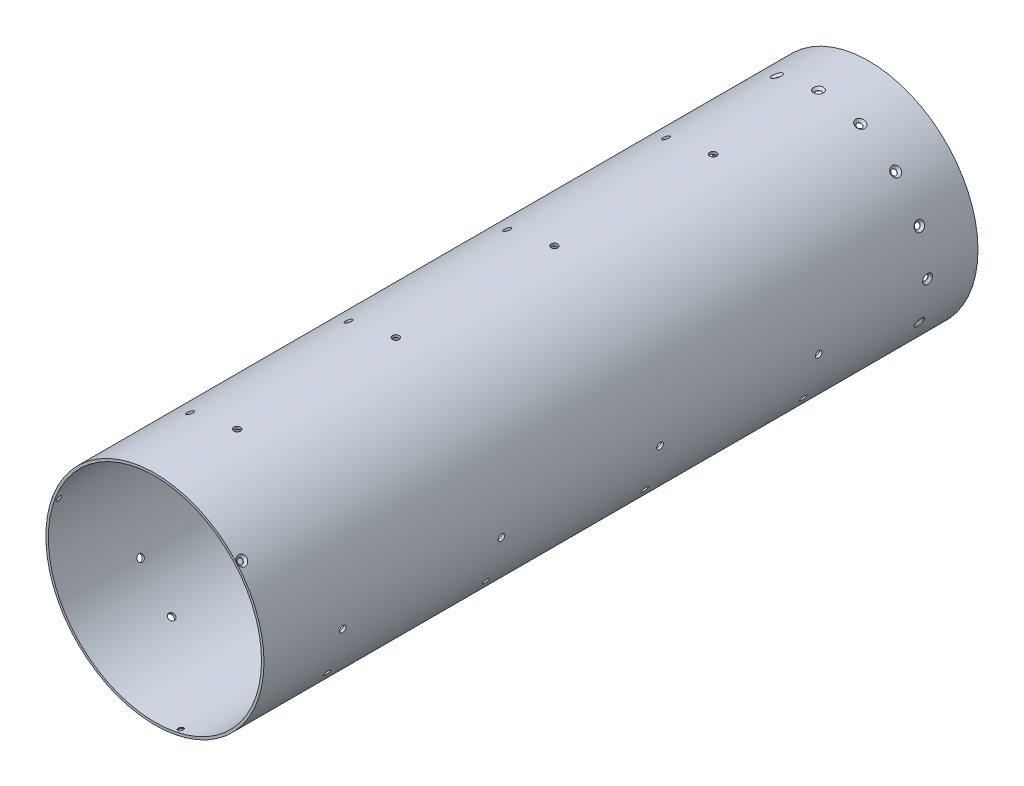
SolidWorks part; units mm, degrees
material "6061-T6 (SS)"
ref_plane "Front Plane" through (0, 0, 0) normal (0, 0, 1) x (1, 0, 0)
ref_plane "Top Plane" through (0, 0, 0) normal (0, 1, 0) x (1, 0, 0)
ref_plane "Right Plane" through (0, 0, 0) normal (1, 0, 0) x (0, 0, -1)
sketch "Sketch1" plane through (0, 0, 0) normal (0, 0, 1) x (1, 0, 0)
  circle A0 centre (0, 0) radius 69.85
  circle A1 centre (0, 0) radius 68.2625
  dimension "D1" = 139.7
  dimension "D2" = 1.5875
extrude "Extrude1" add sketch "Sketch1" along normal blind 457.2
ref_plane "Plane1" through (0, 0, 32.258) normal (0, 0, -1) x (-1, 0, 0)
sketch "Sketch2" plane through (0, 0, 32.258) normal (0, 0, -1) x (-1, 0, 0)
  line L0 (0, 0) -> (0, -69.85) construction
  line L1 (0, 0) -> (-13.6271, -68.5079) construction
  circle A0 centre (0, 0) radius 69.85 construction
  circle A1 centre (0, 0) radius 69.85 construction
  dimension "D1" = 11.25
ref_plane "Plane2" through (0, -69.85, 32.258) normal (0, -1, 0) x (1, 0, 0)
hole_wizard "CSK for M3 Flat Head Machine Screw1" positions "Sketch5" profile "Sketch4" countersink size "M3" standard "Ansi Metric" end condition through all
sketch "Sketch5" plane through (0, -69.85, 32.258) normal (0, -1, 0) x (1, 0, 0)
  point P2 (0, 0)
sketch "Sketch4" plane through (0, -69.85, 32.258) normal (1, 0, 0) x (0, 0, -1)
  line L0 (0, 0) -> (0, 161.1134)
  line L1 (0, 161.1134) -> (1.7, 161.1134)
  line L2 (1.7, 161.1134) -> (1.7, 1.45)
  line L3 (1.7, 1.45) -> (3.15, 0)
  line L5 (3.15, 0) -> (0, 0)
  line L6 (-1.7, 1.45) -> (-3.15, 0) construction
  line L11 (0, -6.35) -> (0, 107.95) construction
  dimension "Thru Hole Dia." = 3.4
  dimension "Thru Hole Depth" = 161.1134
  dimension "Near C'Sink Dia." = 6.3
  dimension "Near C'Sink Angle" = 90
pattern_circular "CirPattern1" count 16 over 360 about axis through (0, 0, 457.2) along (0, 0, -1) of "CSK for M3 Flat Head Machine Screw1"
ref_plane "Plane3" through (0, 0, 446.0875) normal (0, 0, 1) x (1, 0, 0)
ref_plane "Plane5" through (0, 0, 0) normal (0.8315, 0.5556, 0) x (-0.5556, 0.8315, 0)
ref_plane "Plane7" through (0, 0, 0) normal (0.5556, -0.8315, 0) x (0.8315, 0.5556, 0)
ref_plane "Plane9" through (0, 0, 0) normal (-0.1951, -0.9808, 0) x (0.9808, -0.1951, 0)
sketch "Sketch7" plane through (0, 0, 457.2) normal (0, 0, 1) x (1, 0, 0)
  circle A0 centre (0, 0) radius 69.85 construction
  point P0 (69.85, 0)
ref_plane "Plane10" through (13.6271, -68.5079, 32.258) normal (0.1951, -0.9808, 0) x (0.9808, 0.1951, 0)
hole_wizard "#10 Clearance Hole1" positions "Sketch12" profile "Sketch11" hole size "#10" standard "Ansi Inch"
sketch "Sketch12" plane through (13.6271, -68.5079, 32.258) normal (0.1951, -0.9808, 0) x (0.9808, 0.1951, 0)
  point P1 (0, 0)
sketch "Sketch11" plane through (13.6271, -68.5079, 32.258) normal (0, 0, 1) x (0.9808, 0.1951, 0)
  line L0 (0, 0) -> (0, 14.2338)
  line L1 (0, 14.2338) -> (2.5527, 12.7)
  line L2 (2.5527, 12.7) -> (2.5527, 0)
  line L5 (2.5527, 0) -> (0, 0)
  line L10 (0, 14.2338) -> (-2.5527, 12.7) construction
  line L11 (0, -6.35) -> (0, 107.95) construction
  dimension "Hole Dia." = 5.1054
  dimension "Hole Depth" = 12.7
  dimension "Drill Angle" = 118
sketch "Sketch13" plane through (13.6271, -68.5079, 32.258) normal (0.1951, -0.9808, 0) x (0.9808, 0.1951, 0)
  line L0 (0, 0) -> (0, 20.3882) construction
ref_plane "Plane11" through (0, 0, 0) normal (0.9808, 0.1951, 0) x (0, 0, -1)
ref_plane "Plane12" through (0, 0, 454.025) normal (0, 0, 1) x (1, 0, 0)
sketch "Sketch15" plane through (0, 0, 454.025) normal (0, 0, 1) x (1, 0, 0)
  line L0 (0, 0) -> (13.6271, -68.5079) construction
  line L1 (0, 0) -> (0, -69.85) construction
  line L4 (0, -69.8153) -> (0, -68.4) construction
  circle A1 centre (0, 0) radius 69.85 construction
  dimension "D1" = 11.25
ref_plane "Plane13" through (13.6271, -68.5079, 454.025) normal (0.1951, -0.9808, 0) x (0.9808, 0.1951, 0)
hole_wizard "CSK for M3 Flat Head Machine Screw2" positions "Sketch17" profile "Sketch16" countersink size "M3" standard "Ansi Metric"
sketch "Sketch17" plane through (13.6271, -68.5079, 454.025) normal (0.1951, -0.9808, 0) x (0.9808, 0.1951, 0)
  point P7 (0, 0)
sketch "Sketch16" plane through (13.6271, -68.5079, 454.025) normal (0, 0, 1) x (0.9808, 0.1951, 0)
  line L0 (0, 0) -> (0, 8.6415)
  line L1 (0, 8.6415) -> (1.7, 7.62)
  line L2 (1.7, 7.62) -> (1.7, 1.45)
  line L3 (1.7, 1.45) -> (3.15, 0)
  line L5 (3.15, 0) -> (0, 0)
  line L6 (-1.7, 1.45) -> (-3.15, 0) construction
  line L10 (0, 8.6415) -> (-1.7, 7.62) construction
  line L11 (0, -6.35) -> (0, 107.95) construction
  dimension "Hole Dia." = 3.4
  dimension "Hole Depth" = 7.62
  dimension "Near C'Sink Dia." = 6.3
  dimension "Near C'Sink Angle" = 90
  dimension "Drill Angle" = 118
pattern_circular "CirPattern2" count 3 over 360 about axis through (0, 0, 457.2) along (0, 0, -1) of "CSK for M3 Flat Head Machine Screw2"
ref_plane "Plane14" through (0, 0, 406.4) normal (0, 0, 1) x (1, 0, 0)
sketch "Sketch19" plane through (0, 0, 406.4) normal (0, 0, 1) x (1, 0, 0)
  line L0 (0, 0) -> (-13.6271, 68.5079) construction
  line L2 (0, 0) -> (-28.4244, 63.805) construction
  line L3 (0, 0) -> (1.8436, 69.8257) construction
  line L4 (-13.6271, 68.5079) -> (-28.4244, 63.805) construction
  line L5 (-13.6271, 68.5079) -> (1.8436, 69.8257) construction
  line L6 (0, 0) -> (13.6271, -68.5079) construction
  circle A0 centre (0, 0) radius 69.85 construction
  dimension "D1" = 12.762
  dimension "D2" = 30.861
ref_plane "Plane15" through (-28.4244, 63.805, 406.4) normal (-0.4069, 0.9135, 0) x (-0.9135, -0.4069, 0)
ref_plane "Plane16" through (1.8436, 69.8257, 406.4) normal (0.0264, 0.9997, 0) x (-0.9997, 0.0264, 0)
hole_wizard "#6 Clearance Hole1" positions "Sketch21" profile "Sketch22" hole size "#6" standard "Ansi Inch"
sketch "Sketch21" plane through (1.8436, 69.8257, 406.4) normal (0.0264, 0.9997, 0) x (-0.9997, 0.0264, 0)
  point P3 (0, 0)
sketch "Sketch22" plane through (1.8436, 69.8257, 406.4) normal (0, 0, 1) x (-0.9997, 0.0264, 0)
  line L0 (0, 0) -> (0, 13.9934)
  line L1 (0, 13.9934) -> (2.1526, 12.7)
  line L2 (2.1526, 12.7) -> (2.1526, 0)
  line L5 (2.1526, 0) -> (0, 0)
  line L10 (0, 13.9934) -> (-2.1527, 12.7) construction
  line L11 (0, -6.35) -> (0, 107.95) construction
  dimension "Hole Dia." = 4.3053
  dimension "Hole Depth" = 12.7
  dimension "Drill Angle" = 118
hole_wizard "#6 Clearance Hole2" positions "Sketch25" profile "Sketch24" hole size "#6" standard "Ansi Inch"
sketch "Sketch25" plane through (-28.4244, 63.805, 406.4) normal (-0.4069, 0.9135, 0) x (-0.9135, -0.4069, 0)
  point P1 (0, 0)
sketch "Sketch24" plane through (-28.4244, 63.805, 406.4) normal (0, 0, 1) x (-0.9135, -0.4069, 0)
  line L0 (0, 0) -> (0, 13.9934)
  line L1 (0, 13.9934) -> (2.1526, 12.7)
  line L2 (2.1526, 12.7) -> (2.1526, 0)
  line L5 (2.1526, 0) -> (0, 0)
  line L10 (0, 13.9934) -> (-2.1526, 12.7) construction
  line L11 (0, -6.35) -> (0, 107.95) construction
  dimension "Hole Dia." = 4.3053
  dimension "Hole Depth" = 12.7
  dimension "Drill Angle" = 118
pattern_circular "CirPattern3" count 3 over 360 about axis through (0, 0, 457.2) along (0, 0, -1) of "#6 Clearance Hole2", "#6 Clearance Hole1"
pattern_linear "LPattern1" count 4 spacing 101.6 along (0, 0, -1) of "#6 Clearance Hole1", "#6 Clearance Hole2", "CirPattern3"
sketch3d "ref hole"
  line L0 (-40.0918, -55.2068, 101.6) -> (-41.025, -56.4919, 101.6) construction
  spline S0 degree 3 poles (-60.3367, -35.1924, 101.8844) (-60.3367, -35.1924, 101.4578) (-60.3437, -35.1803, 101.3179) (-60.3713, -35.1331, 101.0428) (-60.3921, -35.0973, 100.9061) (-60.4463, -35.0038, 100.6454) (-60.4795, -34.9465, 100.5218) (-60.5575, -34.8111, 100.2878) (-60.6028, -34.7323, 100.177) (-60.7506, -34.4735, 99.8791) (-60.869, -34.2645, 99.7188) (-61.1214, -33.8121, 99.504) (-61.2581, -33.564, 99.4475) (-61.459, -33.1938, 99.4473) (-61.5267, -33.0683, 99.4612) (-61.6569, -32.8248, 99.5162) (-61.7198, -32.7063, 99.5568) (-61.8414, -32.4758, 99.6645) (-61.8999, -32.3641, 99.7319) (-62.0077, -32.1571, 99.8877) (-62.0577, -32.0605, 99.9767) (-62.1497, -31.8817, 100.1775) (-62.1904, -31.8023, 100.2864) (-62.2613, -31.6633, 100.5195) (-62.2918, -31.6032, 100.6453) (-62.3406, -31.5067, 100.9061) (-62.359, -31.4703, 101.0403) (-62.3838, -31.4211, 101.3161) (-62.3902, -31.4084, 101.4588) (-62.3902, -31.4083, 101.7397) (-62.3841, -31.4205, 101.8793) (-62.3594, -31.4696, 102.1568) (-62.3408, -31.5064, 102.293) (-62.2681, -31.6499, 102.6816) (-62.1955, -31.7928, 102.922) (-62.0593, -32.0573, 103.22) (-62.0085, -32.1556, 103.311) (-61.9004, -32.3632, 103.4675) (-61.8431, -32.4727, 103.5337) (-61.7216, -32.7029, 103.6419) (-61.6574, -32.8238, 103.6835) (-61.5276, -33.0665, 103.7385) (-61.4614, -33.1895, 103.7525) (-61.3259, -33.4391, 103.7528) (-61.2586, -33.5623, 103.7389) (-61.1259, -33.8033, 103.6845) (-61.0597, -33.9227, 103.6433) (-60.9325, -34.1507, 103.5354) (-60.8719, -34.2586, 103.4694) (-60.7568, -34.4623, 103.3135) (-60.7019, -34.5587, 103.2226) (-60.6033, -34.7315, 103.0241) (-60.5589, -34.8088, 102.9158) (-60.4803, -34.9452, 102.681) (-60.4466, -35.0034, 102.5554) (-60.3656, -35.143, 102.167) (-60.3367, -35.1924, 101.8844) (-60.3367, -35.1924, 101.4578) (-60.3437, -35.1803, 101.3179) knots -0.0625 -0.0625 0 0 0.03125 0.03125 0.0625 0.0625 0.09375 0.09375 0.125 0.125 0.1875 0.1875 0.25 0.25 0.28125 0.28125 0.3125 0.3125 0.34375 0.34375 0.375 0.375 0.40625 0.40625 0.4375 0.4375 0.46875 0.46875 0.5 0.5 0.53125 0.53125 0.5625 0.5625 0.625 0.625 0.65625 0.65625 0.6875 0.6875 0.71875 0.71875 0.75 0.75 0.78125 0.78125 0.8125 0.8125 0.84375 0.84375 0.875 0.875 0.90625 0.90625 0.9375 0.9375 1 1 1.03125 1.03125 1.0625 only from (-60.3367, -35.1924, 101.6) to (-60.3367, -35.1924, 101.6) construction
  spline S1 degree 3 poles (-39.2832, -57.7568, 101.8844) (-39.2832, -57.7568, 101.4578) (-39.2948, -57.749, 101.3179) (-39.34, -57.7182, 101.0428) (-39.3742, -57.6949, 100.9061) (-39.4635, -57.6339, 100.6454) (-39.518, -57.5965, 100.5218) (-39.6468, -57.5079, 100.2878) (-39.7216, -57.4563, 100.177) (-39.9665, -57.2865, 99.8791) (-40.1634, -57.1489, 99.7188) (-40.5861, -56.8494, 99.504) (-40.8164, -56.6844, 99.4475) (-41.1572, -56.4369, 99.4473) (-41.2723, -56.3528, 99.4612) (-41.4948, -56.1892, 99.5162) (-41.6026, -56.1094, 99.5568) (-41.8117, -55.9537, 99.6645) (-41.9126, -55.8781, 99.7319) (-42.0991, -55.7378, 99.8877) (-42.1858, -55.6722, 99.9767) (-42.3459, -55.5505, 100.1775) (-42.4168, -55.4963, 100.2864) (-42.5407, -55.4015, 100.5195) (-42.5941, -55.3603, 100.6453) (-42.6798, -55.2943, 100.9061) (-42.712, -55.2694, 101.0403) (-42.7556, -55.2357, 101.3161) (-42.7668, -55.227, 101.4588) (-42.7669, -55.227, 101.7397) (-42.7562, -55.2353, 101.8793) (-42.7127, -55.2689, 102.1568) (-42.68, -55.2942, 102.293) (-42.5526, -55.3923, 102.6816) (-42.4255, -55.49, 102.922) (-42.1887, -55.67, 103.22) (-42.1005, -55.7368, 103.311) (-41.9134, -55.8776, 103.4675) (-41.8145, -55.9517, 103.5337) (-41.6057, -56.1071, 103.6419) (-41.4957, -56.1885, 103.6835) (-41.274, -56.3516, 103.7385) (-41.1612, -56.434, 103.7525) (-40.9314, -56.6009, 103.7528) (-40.8175, -56.6831, 103.7389) (-40.594, -56.8434, 103.6845) (-40.4828, -56.9226, 103.6433) (-40.2697, -57.0735, 103.5354) (-40.1686, -57.1448, 103.4694) (-39.9769, -57.279, 103.3135) (-39.8859, -57.3424, 103.2226) (-39.7224, -57.4557, 103.0241) (-39.649, -57.5064, 102.9158) (-39.5193, -57.5956, 102.681) (-39.4639, -57.6336, 102.5554) (-39.3306, -57.7247, 102.167) (-39.2832, -57.7568, 101.8844) (-39.2832, -57.7568, 101.4578) (-39.2948, -57.749, 101.3179) knots -0.0625 -0.0625 0 0 0.03125 0.03125 0.0625 0.0625 0.09375 0.09375 0.125 0.125 0.1875 0.1875 0.25 0.25 0.28125 0.28125 0.3125 0.3125 0.34375 0.34375 0.375 0.375 0.40625 0.40625 0.4375 0.4375 0.46875 0.46875 0.5 0.5 0.53125 0.53125 0.5625 0.5625 0.625 0.625 0.65625 0.65625 0.6875 0.6875 0.71875 0.71875 0.75 0.75 0.78125 0.78125 0.8125 0.8125 0.84375 0.84375 0.875 0.875 0.90625 0.90625 0.9375 0.9375 1 1 1.03125 1.03125 1.0625 only from (-39.2832, -57.7568, 101.6) to (-39.2832, -57.7568, 101.6) construction
  spline S2 degree 3 poles (-60.3367, -35.1924, 101.8844) (-60.3367, -35.1924, 101.4578) (-60.3437, -35.1803, 101.3179) (-60.3713, -35.1331, 101.0428) (-60.3921, -35.0973, 100.9061) (-60.4463, -35.0038, 100.6454) (-60.4795, -34.9465, 100.5218) (-60.5575, -34.8111, 100.2878) (-60.6028, -34.7323, 100.177) (-60.7506, -34.4735, 99.8791) (-60.869, -34.2645, 99.7188) (-61.1214, -33.8121, 99.504) (-61.2581, -33.564, 99.4475) (-61.459, -33.1938, 99.4473) (-61.5267, -33.0683, 99.4612) (-61.6569, -32.8248, 99.5162) (-61.7198, -32.7063, 99.5568) (-61.8414, -32.4758, 99.6645) (-61.8999, -32.3641, 99.7319) (-62.0077, -32.1571, 99.8877) (-62.0577, -32.0605, 99.9767) (-62.1497, -31.8817, 100.1775) (-62.1904, -31.8023, 100.2864) (-62.2613, -31.6633, 100.5195) (-62.2918, -31.6032, 100.6453) (-62.3406, -31.5067, 100.9061) (-62.359, -31.4703, 101.0403) (-62.3838, -31.4211, 101.3161) (-62.3902, -31.4084, 101.4588) (-62.3902, -31.4083, 101.7397) (-62.3841, -31.4205, 101.8793) (-62.3594, -31.4696, 102.1568) (-62.3408, -31.5064, 102.293) (-62.2681, -31.6499, 102.6816) (-62.1955, -31.7928, 102.922) (-62.0593, -32.0573, 103.22) (-62.0085, -32.1556, 103.311) (-61.9004, -32.3632, 103.4675) (-61.8431, -32.4727, 103.5337) (-61.7216, -32.7029, 103.6419) (-61.6574, -32.8238, 103.6835) (-61.5276, -33.0665, 103.7385) (-61.4614, -33.1895, 103.7525) (-61.3259, -33.4391, 103.7528) (-61.2586, -33.5623, 103.7389) (-61.1259, -33.8033, 103.6845) (-61.0597, -33.9227, 103.6433) (-60.9325, -34.1507, 103.5354) (-60.8719, -34.2586, 103.4694) (-60.7568, -34.4623, 103.3135) (-60.7019, -34.5587, 103.2226) (-60.6033, -34.7315, 103.0241) (-60.5589, -34.8088, 102.9158) (-60.4803, -34.9452, 102.681) (-60.4466, -35.0034, 102.5554) (-60.3656, -35.143, 102.167) (-60.3367, -35.1924, 101.8844) (-60.3367, -35.1924, 101.4578) (-60.3437, -35.1803, 101.3179) knots -0.0625 -0.0625 0 0 0.03125 0.03125 0.0625 0.0625 0.09375 0.09375 0.125 0.125 0.1875 0.1875 0.25 0.25 0.28125 0.28125 0.3125 0.3125 0.34375 0.34375 0.375 0.375 0.40625 0.40625 0.4375 0.4375 0.46875 0.46875 0.5 0.5 0.53125 0.53125 0.5625 0.5625 0.625 0.625 0.65625 0.65625 0.6875 0.6875 0.71875 0.71875 0.75 0.75 0.78125 0.78125 0.8125 0.8125 0.84375 0.84375 0.875 0.875 0.90625 0.90625 0.9375 0.9375 1 1 1.03125 1.03125 1.0625 only from (-60.3367, -35.1924, 101.6) to (-60.3367, -35.1924, 101.6)
  spline S3 degree 3 poles (-39.2832, -57.7568, 101.8844) (-39.2832, -57.7568, 101.4578) (-39.2948, -57.749, 101.3179) (-39.34, -57.7182, 101.0428) (-39.3742, -57.6949, 100.9061) (-39.4635, -57.6339, 100.6454) (-39.518, -57.5965, 100.5218) (-39.6468, -57.5079, 100.2878) (-39.7216, -57.4563, 100.177) (-39.9665, -57.2865, 99.8791) (-40.1634, -57.1489, 99.7188) (-40.5861, -56.8494, 99.504) (-40.8164, -56.6844, 99.4475) (-41.1572, -56.4369, 99.4473) (-41.2723, -56.3528, 99.4612) (-41.4948, -56.1892, 99.5162) (-41.6026, -56.1094, 99.5568) (-41.8117, -55.9537, 99.6645) (-41.9126, -55.8781, 99.7319) (-42.0991, -55.7378, 99.8877) (-42.1858, -55.6722, 99.9767) (-42.3459, -55.5505, 100.1775) (-42.4168, -55.4963, 100.2864) (-42.5407, -55.4015, 100.5195) (-42.5941, -55.3603, 100.6453) (-42.6798, -55.2943, 100.9061) (-42.712, -55.2694, 101.0403) (-42.7556, -55.2357, 101.3161) (-42.7668, -55.227, 101.4588) (-42.7669, -55.227, 101.7397) (-42.7562, -55.2353, 101.8793) (-42.7127, -55.2689, 102.1568) (-42.68, -55.2942, 102.293) (-42.5526, -55.3923, 102.6816) (-42.4255, -55.49, 102.922) (-42.1887, -55.67, 103.22) (-42.1005, -55.7368, 103.311) (-41.9134, -55.8776, 103.4675) (-41.8145, -55.9517, 103.5337) (-41.6057, -56.1071, 103.6419) (-41.4957, -56.1885, 103.6835) (-41.274, -56.3516, 103.7385) (-41.1612, -56.434, 103.7525) (-40.9314, -56.6009, 103.7528) (-40.8175, -56.6831, 103.7389) (-40.594, -56.8434, 103.6845) (-40.4828, -56.9226, 103.6433) (-40.2697, -57.0735, 103.5354) (-40.1686, -57.1448, 103.4694) (-39.9769, -57.279, 103.3135) (-39.8859, -57.3424, 103.2226) (-39.7224, -57.4557, 103.0241) (-39.649, -57.5064, 102.9158) (-39.5193, -57.5956, 102.681) (-39.4639, -57.6336, 102.5554) (-39.3306, -57.7247, 102.167) (-39.2832, -57.7568, 101.8844) (-39.2832, -57.7568, 101.4578) (-39.2948, -57.749, 101.3179) knots -0.0625 -0.0625 0 0 0.03125 0.03125 0.0625 0.0625 0.09375 0.09375 0.125 0.125 0.1875 0.1875 0.25 0.25 0.28125 0.28125 0.3125 0.3125 0.34375 0.34375 0.375 0.375 0.40625 0.40625 0.4375 0.4375 0.46875 0.46875 0.5 0.5 0.53125 0.53125 0.5625 0.5625 0.625 0.625 0.65625 0.65625 0.6875 0.6875 0.71875 0.71875 0.75 0.75 0.78125 0.78125 0.8125 0.8125 0.84375 0.84375 0.875 0.875 0.90625 0.90625 0.9375 0.9375 1 1 1.03125 1.03125 1.0625 only from (-39.2832, -57.7568, 101.6) to (-39.2832, -57.7568, 101.6)
  spline S4 degree 3 poles (60.6459, -34.6569, 305.0844) (60.6459, -34.6569, 304.6578) (60.6389, -34.669, 304.5179) (60.6118, -34.7165, 304.2428) (60.5912, -34.7525, 304.1061) (60.5373, -34.8462, 303.8454) (60.5043, -34.9035, 303.7218) (60.4261, -35.0388, 303.4878) (60.3804, -35.1174, 303.377) (60.2303, -35.3748, 303.0791) (60.1084, -35.5818, 302.9188) (59.8429, -36.0266, 302.704) (59.6964, -36.2691, 302.6475) (59.4762, -36.6282, 302.6473) (59.4013, -36.7495, 302.6612) (59.2556, -36.984, 302.7162) (59.1844, -37.0978, 302.7568) (59.0456, -37.3184, 302.8645) (58.9781, -37.4249, 302.9319) (58.8527, -37.6217, 303.0877) (58.7941, -37.7133, 303.1767) (58.6853, -37.8824, 303.3775) (58.6368, -37.9573, 303.4864) (58.5518, -38.0882, 303.7195) (58.515, -38.1447, 303.8453) (58.4559, -38.2352, 304.1061) (58.4336, -38.2693, 304.2403) (58.4033, -38.3154, 304.5161) (58.3956, -38.3273, 304.6588) (58.3955, -38.3273, 304.9397) (58.403, -38.316, 305.0793) (58.4331, -38.27, 305.3568) (58.4558, -38.2355, 305.493) (58.5437, -38.1008, 305.8816) (58.6311, -37.9665, 306.122) (58.7921, -37.7163, 306.42) (58.8518, -37.6232, 306.511) (58.9776, -37.4257, 306.6675) (59.0437, -37.3213, 306.7337) (59.1824, -37.101, 306.8419) (59.255, -36.985, 306.8835) (59.4002, -36.7512, 306.9385) (59.4736, -36.6323, 306.9525) (59.6221, -36.3903, 306.9528) (59.6951, -36.2703, 306.9389) (59.8375, -36.0349, 306.8845) (59.9078, -35.9179, 306.8433) (60.0416, -35.6937, 306.7354) (60.1048, -35.5873, 306.6694) (60.2236, -35.3858, 306.5135) (60.2797, -35.2901, 306.4226) (60.38, -35.1182, 306.2241) (60.4247, -35.0411, 306.1158) (60.5036, -34.9049, 305.881) (60.5371, -34.8466, 305.7554) (60.6175, -34.7066, 305.367) (60.6459, -34.6569, 305.0844) (60.6459, -34.6569, 304.6578) (60.6389, -34.669, 304.5179) knots -0.0625 -0.0625 0 0 0.03125 0.03125 0.0625 0.0625 0.09375 0.09375 0.125 0.125 0.1875 0.1875 0.25 0.25 0.28125 0.28125 0.3125 0.3125 0.34375 0.34375 0.375 0.375 0.40625 0.40625 0.4375 0.4375 0.46875 0.46875 0.5 0.5 0.53125 0.53125 0.5625 0.5625 0.625 0.625 0.65625 0.65625 0.6875 0.6875 0.71875 0.71875 0.75 0.75 0.78125 0.78125 0.8125 0.8125 0.84375 0.84375 0.875 0.875 0.90625 0.90625 0.9375 0.9375 1 1 1.03125 1.03125 1.0625 only from (60.6459, -34.6569, 304.8) to (60.6459, -34.6569, 304.8) construction
  spline S5 degree 3 poles (-60.3367, -35.1924, 305.0844) (-60.3367, -35.1924, 304.6578) (-60.3437, -35.1803, 304.5179) (-60.3713, -35.1331, 304.2428) (-60.3921, -35.0973, 304.1061) (-60.4463, -35.0038, 303.8454) (-60.4795, -34.9465, 303.7218) (-60.5575, -34.8111, 303.4878) (-60.6028, -34.7323, 303.377) (-60.7506, -34.4735, 303.0791) (-60.869, -34.2645, 302.9188) (-61.1214, -33.8121, 302.704) (-61.2581, -33.564, 302.6475) (-61.459, -33.1938, 302.6473) (-61.5267, -33.0683, 302.6612) (-61.6569, -32.8248, 302.7162) (-61.7198, -32.7063, 302.7568) (-61.8414, -32.4758, 302.8645) (-61.8999, -32.3641, 302.9319) (-62.0077, -32.1571, 303.0877) (-62.0577, -32.0605, 303.1767) (-62.1497, -31.8817, 303.3775) (-62.1904, -31.8023, 303.4864) (-62.2613, -31.6633, 303.7195) (-62.2918, -31.6032, 303.8453) (-62.3406, -31.5067, 304.1061) (-62.359, -31.4703, 304.2403) (-62.3838, -31.4211, 304.5161) (-62.3902, -31.4084, 304.6588) (-62.3902, -31.4083, 304.9397) (-62.3841, -31.4205, 305.0793) (-62.3594, -31.4696, 305.3568) (-62.3408, -31.5064, 305.493) (-62.2681, -31.6499, 305.8816) (-62.1955, -31.7928, 306.122) (-62.0593, -32.0573, 306.42) (-62.0085, -32.1556, 306.511) (-61.9004, -32.3632, 306.6675) (-61.8431, -32.4727, 306.7337) (-61.7216, -32.7029, 306.8419) (-61.6574, -32.8238, 306.8835) (-61.5276, -33.0665, 306.9385) (-61.4614, -33.1895, 306.9525) (-61.3259, -33.4391, 306.9528) (-61.2586, -33.5623, 306.9389) (-61.1259, -33.8033, 306.8845) (-61.0597, -33.9227, 306.8433) (-60.9325, -34.1507, 306.7354) (-60.8719, -34.2586, 306.6694) (-60.7568, -34.4623, 306.5135) (-60.7019, -34.5587, 306.4226) (-60.6033, -34.7315, 306.2241) (-60.5589, -34.8088, 306.1158) (-60.4803, -34.9452, 305.881) (-60.4466, -35.0034, 305.7554) (-60.3656, -35.143, 305.367) (-60.3367, -35.1924, 305.0844) (-60.3367, -35.1924, 304.6578) (-60.3437, -35.1803, 304.5179) knots -0.0625 -0.0625 0 0 0.03125 0.03125 0.0625 0.0625 0.09375 0.09375 0.125 0.125 0.1875 0.1875 0.25 0.25 0.28125 0.28125 0.3125 0.3125 0.34375 0.34375 0.375 0.375 0.40625 0.40625 0.4375 0.4375 0.46875 0.46875 0.5 0.5 0.53125 0.53125 0.5625 0.5625 0.625 0.625 0.65625 0.65625 0.6875 0.6875 0.71875 0.71875 0.75 0.75 0.78125 0.78125 0.8125 0.8125 0.84375 0.84375 0.875 0.875 0.90625 0.90625 0.9375 0.9375 1 1 1.03125 1.03125 1.0625 only from (-60.3367, -35.1924, 304.8) to (-60.3367, -35.1924, 304.8) construction
  spline S6 degree 3 poles (-39.2832, -57.7568, 305.0844) (-39.2832, -57.7568, 304.6578) (-39.2948, -57.749, 304.5179) (-39.34, -57.7182, 304.2428) (-39.3742, -57.6949, 304.1061) (-39.4635, -57.6339, 303.8454) (-39.518, -57.5965, 303.7218) (-39.6468, -57.5079, 303.4878) (-39.7216, -57.4563, 303.377) (-39.9665, -57.2865, 303.0791) (-40.1634, -57.1489, 302.9188) (-40.5861, -56.8494, 302.704) (-40.8164, -56.6844, 302.6475) (-41.1572, -56.4369, 302.6473) (-41.2723, -56.3528, 302.6612) (-41.4948, -56.1892, 302.7162) (-41.6026, -56.1094, 302.7568) (-41.8117, -55.9537, 302.8645) (-41.9126, -55.8781, 302.9319) (-42.0991, -55.7378, 303.0877) (-42.1858, -55.6722, 303.1767) (-42.3459, -55.5505, 303.3775) (-42.4168, -55.4963, 303.4864) (-42.5407, -55.4015, 303.7195) (-42.5941, -55.3603, 303.8453) (-42.6798, -55.2943, 304.1061) (-42.712, -55.2694, 304.2403) (-42.7556, -55.2357, 304.5161) (-42.7668, -55.227, 304.6588) (-42.7669, -55.227, 304.9397) (-42.7562, -55.2353, 305.0793) (-42.7127, -55.2689, 305.3568) (-42.68, -55.2942, 305.493) (-42.5526, -55.3923, 305.8816) (-42.4255, -55.49, 306.122) (-42.1887, -55.67, 306.42) (-42.1005, -55.7368, 306.511) (-41.9134, -55.8776, 306.6675) (-41.8145, -55.9517, 306.7337) (-41.6057, -56.1071, 306.8419) (-41.4957, -56.1885, 306.8835) (-41.274, -56.3516, 306.9385) (-41.1612, -56.434, 306.9525) (-40.9314, -56.6009, 306.9528) (-40.8175, -56.6831, 306.9389) (-40.594, -56.8434, 306.8845) (-40.4828, -56.9226, 306.8433) (-40.2697, -57.0735, 306.7354) (-40.1686, -57.1448, 306.6694) (-39.9769, -57.279, 306.5135) (-39.8859, -57.3424, 306.4226) (-39.7224, -57.4557, 306.2241) (-39.649, -57.5064, 306.1158) (-39.5193, -57.5956, 305.881) (-39.4639, -57.6336, 305.7554) (-39.3306, -57.7247, 305.367) (-39.2832, -57.7568, 305.0844) (-39.2832, -57.7568, 304.6578) (-39.2948, -57.749, 304.5179) knots -0.0625 -0.0625 0 0 0.03125 0.03125 0.0625 0.0625 0.09375 0.09375 0.125 0.125 0.1875 0.1875 0.25 0.25 0.28125 0.28125 0.3125 0.3125 0.34375 0.34375 0.375 0.375 0.40625 0.40625 0.4375 0.4375 0.46875 0.46875 0.5 0.5 0.53125 0.53125 0.5625 0.5625 0.625 0.625 0.65625 0.65625 0.6875 0.6875 0.71875 0.71875 0.75 0.75 0.78125 0.78125 0.8125 0.8125 0.84375 0.84375 0.875 0.875 0.90625 0.90625 0.9375 0.9375 1 1 1.03125 1.03125 1.0625 only from (-39.2832, -57.7568, 304.8) to (-39.2832, -57.7568, 304.8) construction
  spline S7 degree 3 poles (60.6459, -34.6569, 305.0844) (60.6459, -34.6569, 304.6578) (60.6389, -34.669, 304.5179) (60.6118, -34.7165, 304.2428) (60.5912, -34.7525, 304.1061) (60.5373, -34.8462, 303.8454) (60.5043, -34.9035, 303.7218) (60.4261, -35.0388, 303.4878) (60.3804, -35.1174, 303.377) (60.2303, -35.3748, 303.0791) (60.1084, -35.5818, 302.9188) (59.8429, -36.0266, 302.704) (59.6964, -36.2691, 302.6475) (59.4762, -36.6282, 302.6473) (59.4013, -36.7495, 302.6612) (59.2556, -36.984, 302.7162) (59.1844, -37.0978, 302.7568) (59.0456, -37.3184, 302.8645) (58.9781, -37.4249, 302.9319) (58.8527, -37.6217, 303.0877) (58.7941, -37.7133, 303.1767) (58.6853, -37.8824, 303.3775) (58.6368, -37.9573, 303.4864) (58.5518, -38.0882, 303.7195) (58.515, -38.1447, 303.8453) (58.4559, -38.2352, 304.1061) (58.4336, -38.2693, 304.2403) (58.4033, -38.3154, 304.5161) (58.3956, -38.3273, 304.6588) (58.3955, -38.3273, 304.9397) (58.403, -38.316, 305.0793) (58.4331, -38.27, 305.3568) (58.4558, -38.2355, 305.493) (58.5437, -38.1008, 305.8816) (58.6311, -37.9665, 306.122) (58.7921, -37.7163, 306.42) (58.8518, -37.6232, 306.511) (58.9776, -37.4257, 306.6675) (59.0437, -37.3213, 306.7337) (59.1824, -37.101, 306.8419) (59.255, -36.985, 306.8835) (59.4002, -36.7512, 306.9385) (59.4736, -36.6323, 306.9525) (59.6221, -36.3903, 306.9528) (59.6951, -36.2703, 306.9389) (59.8375, -36.0349, 306.8845) (59.9078, -35.9179, 306.8433) (60.0416, -35.6937, 306.7354) (60.1048, -35.5873, 306.6694) (60.2236, -35.3858, 306.5135) (60.2797, -35.2901, 306.4226) (60.38, -35.1182, 306.2241) (60.4247, -35.0411, 306.1158) (60.5036, -34.9049, 305.881) (60.5371, -34.8466, 305.7554) (60.6175, -34.7066, 305.367) (60.6459, -34.6569, 305.0844) (60.6459, -34.6569, 304.6578) (60.6389, -34.669, 304.5179) knots -0.0625 -0.0625 0 0 0.03125 0.03125 0.0625 0.0625 0.09375 0.09375 0.125 0.125 0.1875 0.1875 0.25 0.25 0.28125 0.28125 0.3125 0.3125 0.34375 0.34375 0.375 0.375 0.40625 0.40625 0.4375 0.4375 0.46875 0.46875 0.5 0.5 0.53125 0.53125 0.5625 0.5625 0.625 0.625 0.65625 0.65625 0.6875 0.6875 0.71875 0.71875 0.75 0.75 0.78125 0.78125 0.8125 0.8125 0.84375 0.84375 0.875 0.875 0.90625 0.90625 0.9375 0.9375 1 1 1.03125 1.03125 1.0625 only from (60.6459, -34.6569, 304.8) to (60.6459, -34.6569, 304.8)
  spline S8 degree 3 poles (-60.3367, -35.1924, 305.0844) (-60.3367, -35.1924, 304.6578) (-60.3437, -35.1803, 304.5179) (-60.3713, -35.1331, 304.2428) (-60.3921, -35.0973, 304.1061) (-60.4463, -35.0038, 303.8454) (-60.4795, -34.9465, 303.7218) (-60.5575, -34.8111, 303.4878) (-60.6028, -34.7323, 303.377) (-60.7506, -34.4735, 303.0791) (-60.869, -34.2645, 302.9188) (-61.1214, -33.8121, 302.704) (-61.2581, -33.564, 302.6475) (-61.459, -33.1938, 302.6473) (-61.5267, -33.0683, 302.6612) (-61.6569, -32.8248, 302.7162) (-61.7198, -32.7063, 302.7568) (-61.8414, -32.4758, 302.8645) (-61.8999, -32.3641, 302.9319) (-62.0077, -32.1571, 303.0877) (-62.0577, -32.0605, 303.1767) (-62.1497, -31.8817, 303.3775) (-62.1904, -31.8023, 303.4864) (-62.2613, -31.6633, 303.7195) (-62.2918, -31.6032, 303.8453) (-62.3406, -31.5067, 304.1061) (-62.359, -31.4703, 304.2403) (-62.3838, -31.4211, 304.5161) (-62.3902, -31.4084, 304.6588) (-62.3902, -31.4083, 304.9397) (-62.3841, -31.4205, 305.0793) (-62.3594, -31.4696, 305.3568) (-62.3408, -31.5064, 305.493) (-62.2681, -31.6499, 305.8816) (-62.1955, -31.7928, 306.122) (-62.0593, -32.0573, 306.42) (-62.0085, -32.1556, 306.511) (-61.9004, -32.3632, 306.6675) (-61.8431, -32.4727, 306.7337) (-61.7216, -32.7029, 306.8419) (-61.6574, -32.8238, 306.8835) (-61.5276, -33.0665, 306.9385) (-61.4614, -33.1895, 306.9525) (-61.3259, -33.4391, 306.9528) (-61.2586, -33.5623, 306.9389) (-61.1259, -33.8033, 306.8845) (-61.0597, -33.9227, 306.8433) (-60.9325, -34.1507, 306.7354) (-60.8719, -34.2586, 306.6694) (-60.7568, -34.4623, 306.5135) (-60.7019, -34.5587, 306.4226) (-60.6033, -34.7315, 306.2241) (-60.5589, -34.8088, 306.1158) (-60.4803, -34.9452, 305.881) (-60.4466, -35.0034, 305.7554) (-60.3656, -35.143, 305.367) (-60.3367, -35.1924, 305.0844) (-60.3367, -35.1924, 304.6578) (-60.3437, -35.1803, 304.5179) knots -0.0625 -0.0625 0 0 0.03125 0.03125 0.0625 0.0625 0.09375 0.09375 0.125 0.125 0.1875 0.1875 0.25 0.25 0.28125 0.28125 0.3125 0.3125 0.34375 0.34375 0.375 0.375 0.40625 0.40625 0.4375 0.4375 0.46875 0.46875 0.5 0.5 0.53125 0.53125 0.5625 0.5625 0.625 0.625 0.65625 0.65625 0.6875 0.6875 0.71875 0.71875 0.75 0.75 0.78125 0.78125 0.8125 0.8125 0.84375 0.84375 0.875 0.875 0.90625 0.90625 0.9375 0.9375 1 1 1.03125 1.03125 1.0625 only from (-60.3367, -35.1924, 304.8) to (-60.3367, -35.1924, 304.8)
  spline S9 degree 3 poles (-39.2832, -57.7568, 305.0844) (-39.2832, -57.7568, 304.6578) (-39.2948, -57.749, 304.5179) (-39.34, -57.7182, 304.2428) (-39.3742, -57.6949, 304.1061) (-39.4635, -57.6339, 303.8454) (-39.518, -57.5965, 303.7218) (-39.6468, -57.5079, 303.4878) (-39.7216, -57.4563, 303.377) (-39.9665, -57.2865, 303.0791) (-40.1634, -57.1489, 302.9188) (-40.5861, -56.8494, 302.704) (-40.8164, -56.6844, 302.6475) (-41.1572, -56.4369, 302.6473) (-41.2723, -56.3528, 302.6612) (-41.4948, -56.1892, 302.7162) (-41.6026, -56.1094, 302.7568) (-41.8117, -55.9537, 302.8645) (-41.9126, -55.8781, 302.9319) (-42.0991, -55.7378, 303.0877) (-42.1858, -55.6722, 303.1767) (-42.3459, -55.5505, 303.3775) (-42.4168, -55.4963, 303.4864) (-42.5407, -55.4015, 303.7195) (-42.5941, -55.3603, 303.8453) (-42.6798, -55.2943, 304.1061) (-42.712, -55.2694, 304.2403) (-42.7556, -55.2357, 304.5161) (-42.7668, -55.227, 304.6588) (-42.7669, -55.227, 304.9397) (-42.7562, -55.2353, 305.0793) (-42.7127, -55.2689, 305.3568) (-42.68, -55.2942, 305.493) (-42.5526, -55.3923, 305.8816) (-42.4255, -55.49, 306.122) (-42.1887, -55.67, 306.42) (-42.1005, -55.7368, 306.511) (-41.9134, -55.8776, 306.6675) (-41.8145, -55.9517, 306.7337) (-41.6057, -56.1071, 306.8419) (-41.4957, -56.1885, 306.8835) (-41.274, -56.3516, 306.9385) (-41.1612, -56.434, 306.9525) (-40.9314, -56.6009, 306.9528) (-40.8175, -56.6831, 306.9389) (-40.594, -56.8434, 306.8845) (-40.4828, -56.9226, 306.8433) (-40.2697, -57.0735, 306.7354) (-40.1686, -57.1448, 306.6694) (-39.9769, -57.279, 306.5135) (-39.8859, -57.3424, 306.4226) (-39.7224, -57.4557, 306.2241) (-39.649, -57.5064, 306.1158) (-39.5193, -57.5956, 305.881) (-39.4639, -57.6336, 305.7554) (-39.3306, -57.7247, 305.367) (-39.2832, -57.7568, 305.0844) (-39.2832, -57.7568, 304.6578) (-39.2948, -57.749, 304.5179) knots -0.0625 -0.0625 0 0 0.03125 0.03125 0.0625 0.0625 0.09375 0.09375 0.125 0.125 0.1875 0.1875 0.25 0.25 0.28125 0.28125 0.3125 0.3125 0.34375 0.34375 0.375 0.375 0.40625 0.40625 0.4375 0.4375 0.46875 0.46875 0.5 0.5 0.53125 0.53125 0.5625 0.5625 0.625 0.625 0.65625 0.65625 0.6875 0.6875 0.71875 0.71875 0.75 0.75 0.78125 0.78125 0.8125 0.8125 0.84375 0.84375 0.875 0.875 0.90625 0.90625 0.9375 0.9375 1 1 1.03125 1.03125 1.0625 only from (-39.2832, -57.7568, 304.8) to (-39.2832, -57.7568, 304.8)
  point P2 (-40.9926, -56.4472, 101.6)
